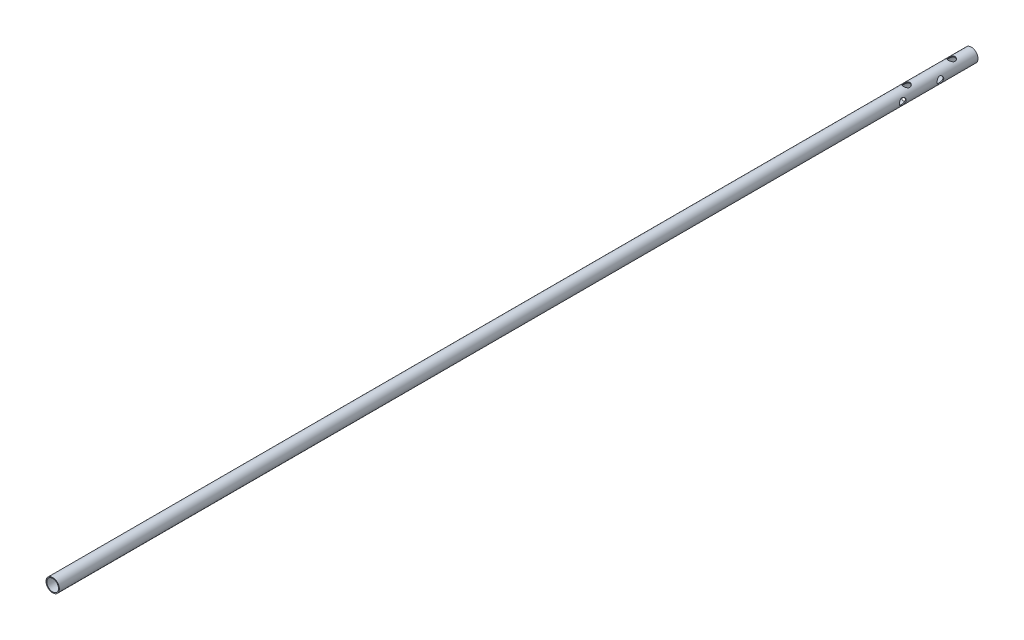
SolidWorks part; units mm, degrees
material "carbon fiber"
ref_plane "Front Plane" through (0, 0, 0) normal (0, 0, 1) x (1, 0, 0)
ref_plane "Top Plane" through (0, 0, 0) normal (0, 1, 0) x (1, 0, 0)
ref_plane "Right Plane" through (0, 0, 0) normal (1, 0, 0) x (0, 0, -1)
sketch "Эскиз1" plane through (0, 0, 0) normal (0, 0, 1) x (1, 0, 0)
  circle A0 centre (0, 0) radius 8
  circle A1 centre (0, 0) radius 7
  dimension "D1" = 16
  dimension "D2" = 1
extrude "Бобышка-Вытянуть1" add sketch "Эскиз1" along normal mid plane 1100
sketch "Эскиз2" plane through (0, 0, 0) normal (1, 0, 0) x (0, 0, -1)
  line L0 (620.3264, 0) -> (366.7106, 0) construction
  line L1 (550, -8) -> (550, 8) construction
  circle A0 centre (460, 0) radius 4
  circle A1 centre (505, 0) radius 4
  dimension "D1" = 8
  dimension "D2" = 8
  dimension "D3" = 45
  dimension "D4" = 90
  dimension "D5" = 45
extrude "Вырез-Вытянуть1" cut sketch "Эскиз2" against normal through all both and the other way through all
sketch "Эскиз3" plane through (0, 0, 0) normal (0, 1, 0) x (1, 0, 0)
  line L0 (0, 550) -> (0, 479.9801) construction
  line L1 (7, 550) -> (-7, 550) construction
  circle A0 centre (0, 505) radius 3.2304 construction
  circle A1 centre (0, 526.5) radius 4
  circle A2 centre (0, 472.5) radius 4
  dimension "D1" = 45
  dimension "D2" = 21.5
  dimension "D3" = 8
  dimension "D4" = 54
extrude "Вырез-Вытянуть2" cut sketch "Эскиз3" against normal through all both and the other way through all
